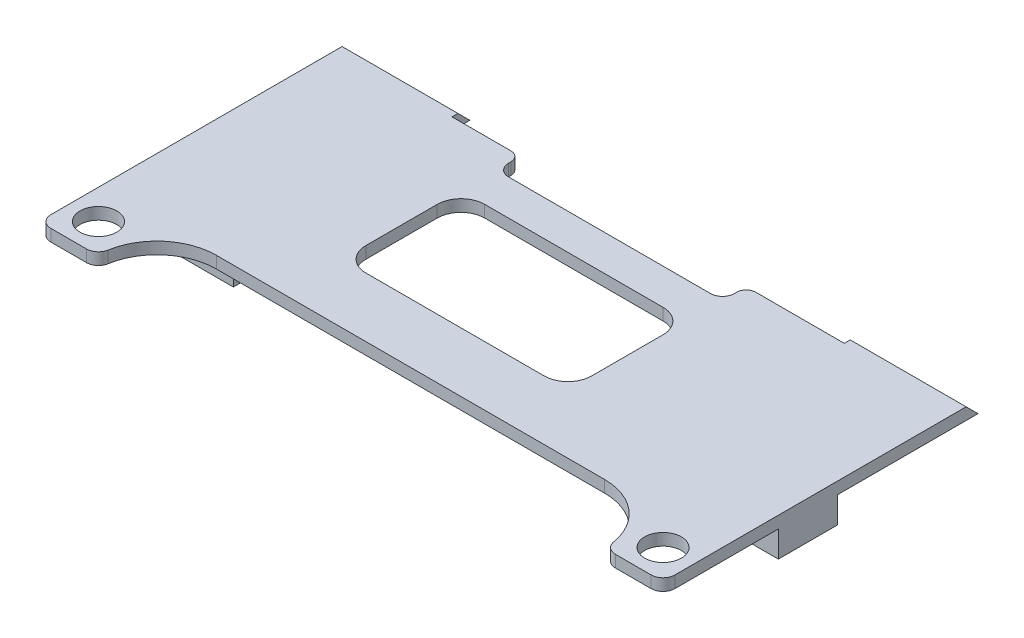
SolidWorks part; units mm, degrees
ref_plane "Front Plane" through (0, 0, 0) normal (0, 0, 1) x (1, 0, 0)
ref_plane "Top Plane" through (0, 0, 0) normal (0, 1, 0) x (1, 0, 0)
ref_plane "Right Plane" through (0, 0, 0) normal (1, 0, 0) x (0, 0, -1)
sketch "Sketch1" plane through (0, 0, 0) normal (0, 1, 0) x (1, 0, 0)
  line L0 (-26.25, 10) -> (-26.25, 12)
  line L1 (-26.25, -10) -> (26.25, -10)
  line L2 (-26.25, -10) -> (-26.25, 10)
  line L3 (-26.25, 10) -> (-11.55, 10)
  line L4 (26.25, -10) -> (26.25, 10)
  line L5 (-26.25, -10) -> (26.25, 10) construction
  line L6 (-26.25, 10) -> (26.25, -10) construction
  line L7 (-26.25, 12) -> (-16.5, 12)
  line L8 (-16.5, 12) -> (-16.5, 10)
  line L9 (16.5, 10) -> (16.5, 12)
  line L10 (16.5, 12) -> (26.25, 12)
  line L11 (26.25, 12) -> (26.25, 10)
  line L12 (8.25, 9.2) -> (8.25, 9)
  line L13 (7.25, 8) -> (-9.75, 8)
  line L14 (-10.75, 9) -> (-10.75, 9.2)
  line L15 (-26.25, -10) -> (-26.25, -14)
  line L16 (-25.25, -15) -> (-22.25, -15)
  line L17 (-21.25, -14) -> (-21.25, -10)
  line L18 (0, -14.85) -> (0, 14.85) construction
  line L19 (25.25, -15) -> (22.25, -15)
  line L20 (26.25, -10) -> (26.25, -14)
  line L21 (21.25, -14) -> (21.25, -10)
  line L22 (9.05, 10) -> (26.25, 10)
  line L23 (-8.75, -5) -> (6.25, -5)
  line L26 (-10.75, -3) -> (-10.75, 3)
  line L27 (-8.75, 5) -> (6.25, 5)
  line L28 (8.25, -3) -> (8.25, 3)
  circle A0 centre (-23.75, -12.5) radius 1.55
  circle A1 centre (23.75, -12.5) radius 1.55
  arc A2 (-8.75, -5) -> (-10.75, -3) centre (-8.75, -3) cw
  arc A3 (6.25, -5) -> (8.25, -3) centre (6.25, -3) ccw
  arc A4 (6.25, 5) -> (8.25, 3) centre (6.25, 3) cw
  arc A5 (-10.75, 3) -> (-8.75, 5) centre (-8.75, 3) cw
  arc A6 (8.25, 9) -> (7.25, 8) centre (7.25, 9) cw
  arc A7 (-9.75, 8) -> (-10.75, 9) centre (-9.75, 9) cw
  arc A8 (8.25, 9.2) -> (9.05, 10) centre (9.05, 9.2) cw
  arc A9 (-10.75, 9.2) -> (-11.55, 10) centre (-11.55, 9.2) ccw
  arc A10 (25.25, -15) -> (26.25, -14) centre (25.25, -14) ccw
  arc A11 (22.25, -15) -> (21.25, -14) centre (22.25, -14) cw
  arc A12 (-26.25, -14) -> (-25.25, -15) centre (-25.25, -14) ccw
  arc A13 (-22.25, -15) -> (-21.25, -14) centre (-22.25, -14) ccw
  point P0 (0, 0)
  point P50 (8.25, 10)
  point P55 (26.25, -15)
  point P58 (21.25, -15)
  point P61 (-26.25, -15)
  point P64 (-21.25, -15)
  dimension "D9" = 2.5
  dimension "D10" = 3.1
  dimension "D17" = 2
  dimension "D18" = 1
  dimension "D19" = 0.8
  dimension "D20" = 1
  dimension "D1" = 2
  dimension "D2" = 33
  dimension "D3" = 18
  dimension "D4" = 9.75
  dimension "D5" = 5
  dimension "D6" = 5
  dimension "D7" = 20
  dimension "D8" = 2.5
  dimension "D11" = 37
  dimension "D12" = 2
  dimension "D15" = 10
  dimension "D16" = 5
extrude "Boss-Extrude1" add sketch "Sketch1" along normal blind 1
chamfer "Chamfer1" distance 1.5 angle 45 4 edges at (21.375, 0, -12) (21.375, 1, -12) (-21.375, 0, -12) (-21.375, 1, -12)
sketch "Sketch5" plane through (0, 0, 0) normal (0, -1, 0) x (1, 0, 0)
  line L0 (-26.25, 8.4) -> (26.25, 8.4)
  line L1 (-26.25, 14) -> (-26.25, -11.5) construction
  line L2 (26.25, 14) -> (26.25, -11.5) construction
  line L3 (-25.25, 15) -> (-22.25, 15) construction
  line L4 (-16.5, -8.9) -> (-16.5, 8.4)
  line L6 (-26.25, 8.4) -> (-26.25, -8.9)
  line L7 (-26.25, -8.9) -> (-16.5, -8.9)
  line L8 (-26.25, -10) -> (-11.55, -10) construction
  line L10 (0, -14.85) -> (0, 14.85) construction
  line L11 (26.25, -8.9) -> (16.5, -8.9)
  line L12 (26.25, 8.4) -> (26.25, -8.9)
  line L13 (16.5, -8.9) -> (16.5, 8.4)
  line L14 (16.5, 0.3) -> (26.25, 0.3)
  line L15 (16.5, 5.3) -> (26.25, 5.3)
  dimension "D1" = 6.6
  dimension "D2" = 1.1
  dimension "D3" = 3.1
  dimension "D4" = 5
  dimension "D5" = 9.75
extrude "Boss-Extrude2" add sketch "Sketch5" along normal blind 2.2
fillet "Fillet2" radius 5 2 edges at (21.25, 0.5, 10) (-21.25, 0.5, 10)
